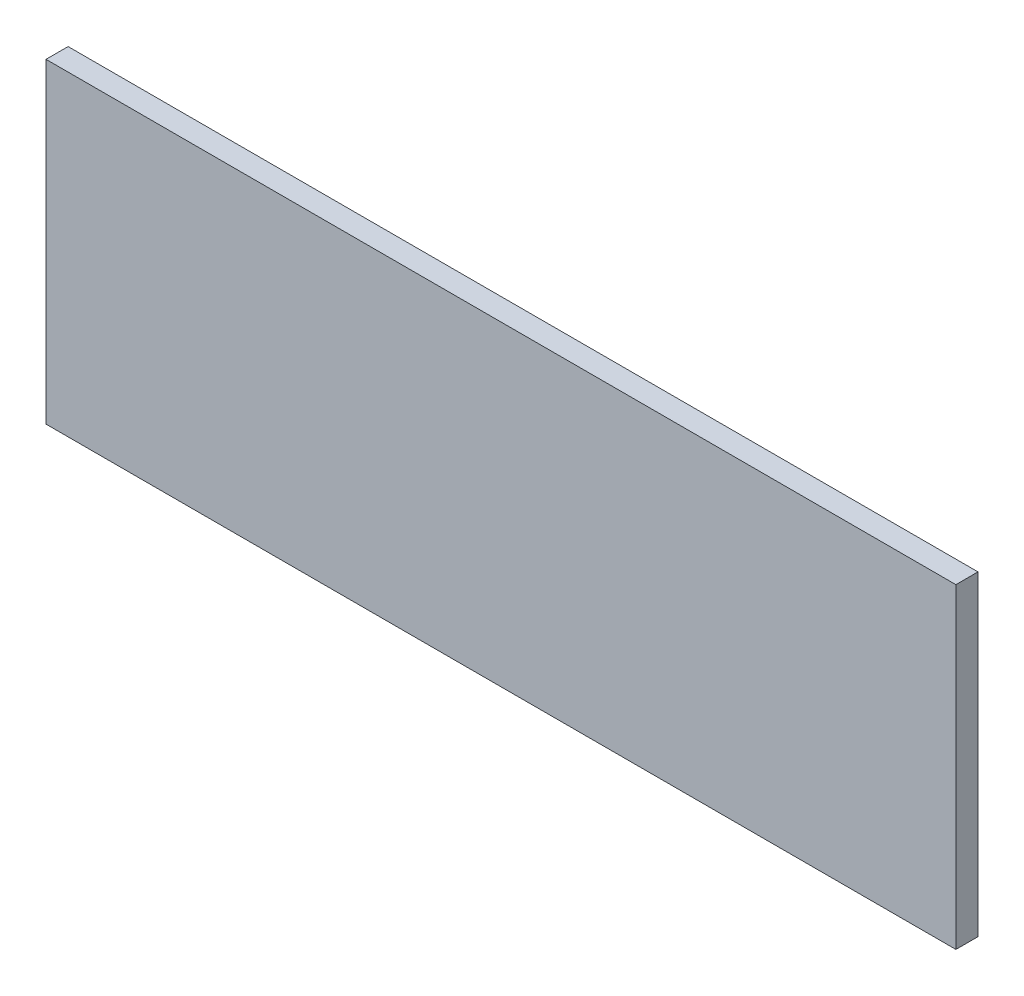
SolidWorks part; units mm, degrees
material "Beech"
ref_plane "Front Plane" through (0, 0, 0) normal (0, 0, 1) x (1, 0, 0)
ref_plane "Top Plane" through (0, 0, 0) normal (0, 1, 0) x (1, 0, 0)
ref_plane "Right Plane" through (0, 0, 0) normal (1, 0, 0) x (0, 0, -1)
sketch "Sketch1" plane through (0, 0, 0) normal (0, 0, 1) x (1, 0, 0)
  line L1 (914.4, 317.5) -> (-914.4, 317.5)
  line L2 (914.4, 317.5) -> (914.4, -317.5)
  line L3 (914.4, -317.5) -> (-914.4, -317.5)
  line L4 (-914.4, 317.5) -> (-914.4, -317.5)
  line L5 (914.4, 317.5) -> (-914.4, -317.5) construction
  line L6 (914.4, -317.5) -> (-914.4, 317.5) construction
  point P0 (0, 0)
  dimension "D1" = 1828.8
  dimension "D2" = 635
extrude "Boss-Extrude1" add sketch "Sketch1" against normal blind 44.45
equation "\"altitude_horizontal_rail_length\"=10in"
equation "\"altitude_vertictal_rail_length\"=12in"
equation "\"table_length\"=72in"
equation "\"table_width\"=25in"
equation "\"table_thickness\"=1.75in"
equation "\"D2@Sketch1\"=\"table_width\""
equation "\"D1@Sketch1\"=\"table_length\""
equation "\"D1@Boss-Extrude1\"=\"table_thickness\""
